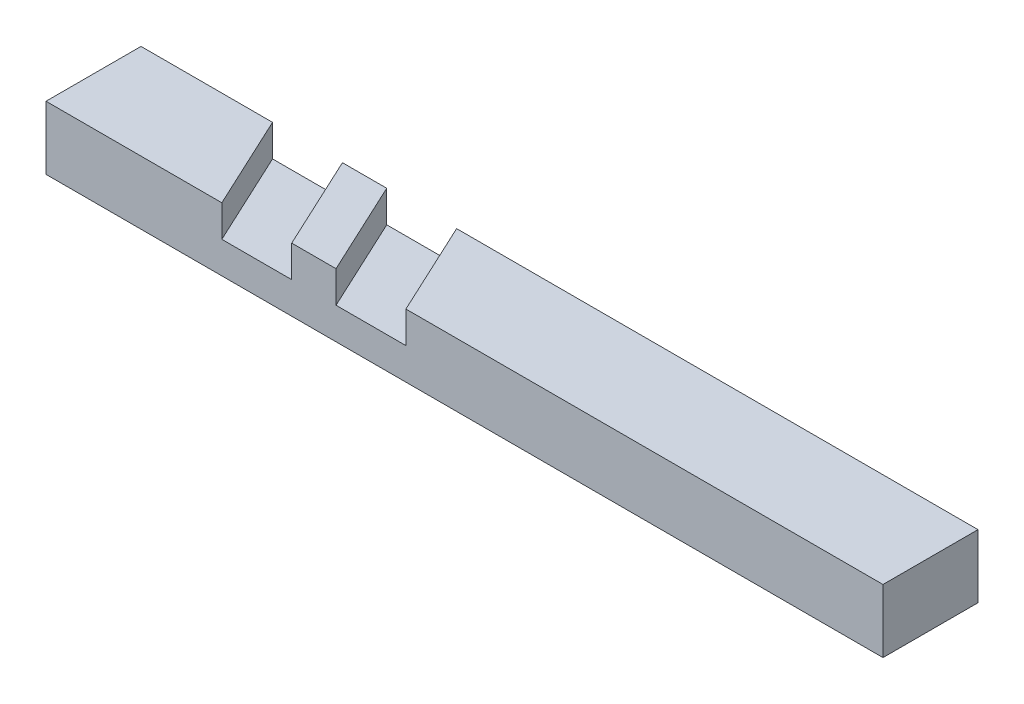
SolidWorks part; units mm, degrees
ref_plane "Front Plane" through (0, 0, 0) normal (0, 0, 1) x (1, 0, 0)
ref_plane "Top Plane" through (0, 0, 0) normal (0, 1, 0) x (1, 0, 0)
ref_plane "Right Plane" through (0, 0, 0) normal (1, 0, 0) x (0, 0, -1)
sketch "Sketch1" plane through (0, 0, 0) normal (0, 1, 0) x (1, 0, 0)
  line L0 (-130.6551, 15) -> (-130.6551, 0)
  line L1 (-130.6551, 0) -> (1.4898, 0)
  line L2 (1.4898, 15) -> (1.4898, 0)
  line L3 (-109.8882, 15) -> (-102.8936, 0)
  line L4 (-130.6551, 15) -> (1.4898, 15)
  line L5 (-98.8544, 15) -> (-91.8598, 0)
  line L6 (-91.8598, 15) -> (-84.8652, 0)
  line L7 (-80.826, 15) -> (-73.8314, 0)
  point P13 (0, 0)
  point P14 (-88.0142, 15)
  point P15 (-92.014, 0)
  point P16 (-102.8936, 0)
  dimension "D1" = 10
  dimension "D2" = 65
  dimension "D3" = 15
  dimension "D4" = 10
extrude "Boss-Extrude1" add sketch "Sketch1" against normal blind 5 contours L4 L0 L1 L3 | L5 L4 L3 L1 | L6 L4 L5 L1 | L7 L4 L6 L1 | L4 L7 L1 L2 region at (-118.439, 0, -7.1397) region at (-100.874, 0, -7.5) region at (-91.8598, 0, -7.5) region at (-82.8456, 0, -7.5) region at (-37.9453, 0, -7.6109)
extrude "Boss-Extrude2" add sketch "Sketch1<3>" along normal blind 5 contours L4 L0 L1 L3 | L6 L4 L5 L1 | L4 L7 L1 L2 region at (-118.439, 0, -7.1397) region at (-91.8598, 0, -7.5) region at (-37.9453, 0, -7.6109)
sketch "Sketch1<3>" plane through (0, 0, 0) normal (0, 1, 0) x (1, 0, 0) same geometry as "Sketch1"
